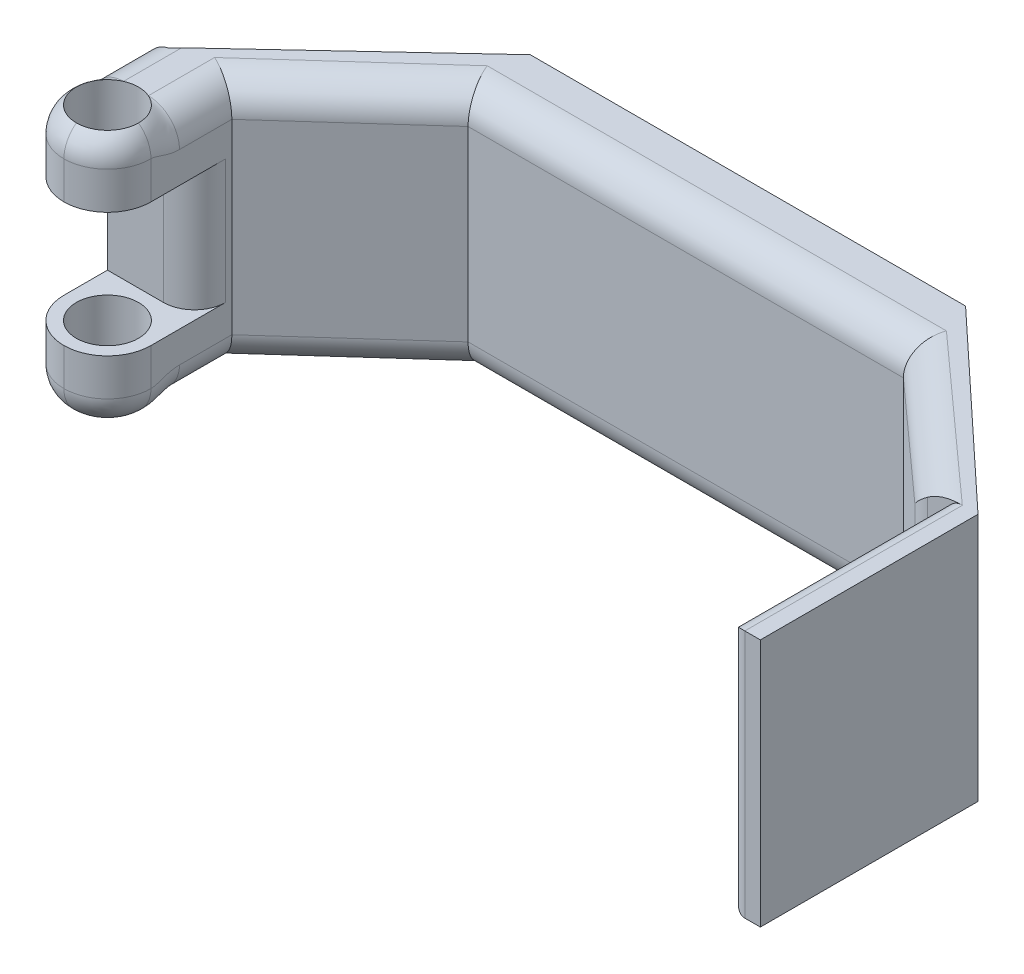
SolidWorks part; units mm, degrees
ref_plane "Front Plane" through (0, 0, 0) normal (0, 0, 1) x (1, 0, 0)
ref_plane "Top Plane" through (0, 0, 0) normal (0, 1, 0) x (1, 0, 0)
ref_plane "Right Plane" through (0, 0, 0) normal (1, 0, 0) x (0, 0, -1)
sketch "Sketch1" plane through (0, 0, 0) normal (0, 1, 0) x (1, 0, 0)
  line L0 (0, 0) -> (20, 18)
  line L1 (20, 18) -> (90, 18)
  line L2 (90, 18) -> (110, 0)
  line L3 (0, 0) -> (-10, 0)
  line L4 (-10, 0) -> (20, 28)
  line L5 (20, 28) -> (90, 28)
  line L6 (110, 0) -> (120, 0)
  line L7 (120, 0) -> (90, 28)
  dimension "D1" = 20
  dimension "D2" = 18
  dimension "D3" = 70
  dimension "D4" = 20
  dimension "D5" = 18
  dimension "D6" = 10
  dimension "D7" = 10
  dimension "D8" = 10
extrude "Boss-Extrude1" add sketch "Sketch1" along normal blind 40
sketch "Sketch2" plane through (0, 0, 0) normal (0, 0, 1) x (1, 0, 0)
  line L1 (0, 40) -> (-14, 40)
  line L2 (0, 40) -> (0, 0)
  line L3 (0, 0) -> (-14, 0)
  line L4 (-14, 40) -> (-14, 0)
  dimension "D1" = 14
extrude "Boss-Extrude2" add sketch "Sketch2" along normal blind 20
sketch "Sketch3" plane through (0, 0, 0) normal (1, 0, 0) x (0, 0, -1)
  line L0 (-20, 0) -> (-20, 40) construction
  line L1 (-20, 30) -> (-6, 30)
  line L2 (-20, 30) -> (-20, 10)
  line L3 (-20, 10) -> (-6, 10)
  line L4 (-6, 30) -> (-6, 10)
  line L5 (-20, 0) -> (0, 0) construction
  dimension "D1" = 14
  dimension "D2" = 20
  dimension "D3" = 10
extrude "Cut-Extrude2" cut sketch "Sketch3" against normal up to next
sketch "Sketch5" plane through (0, 10, 0) normal (0, 1, 0) x (1, 0, 0)
  circle A0 centre (-7, -13) radius 5
  dimension "D1" = 10
extrude "Cut-Extrude3" cut sketch "Sketch5" against normal through all and the other way through all
fillet "Fillet1" radius 7 4 edges at (-14, 5, 20) (0, 5, 20) (0, 35, 20) (-14, 35, 20)
sketch "Sketch7" plane through (0, 0, 0) normal (0, 0, 1) x (1, 0, 0)
  line L0 (110, 0) -> (120, 0) construction
  line L1 (120, 40) -> (115, 40)
  line L2 (120, 40) -> (120, 0)
  line L3 (120, 0) -> (115, 0)
  line L4 (115, 40) -> (115, 0)
extrude "Boss-Extrude3" add sketch "Sketch7" along normal blind 35
fillet "Fillet2" radius 5 12 edges at (0, 0, 6.5) (-14, 0, 6.5) (-14, 40, 6.5) (0, 40, 6.5) (0, 20, 6) (110, 20, 0) (100, 40, -9) (100, 0, -9) (55, 0, -18) (10, 0, -9) (55, 40, -18) (10, 40, -9)
fillet "Fillet3" radius 2.5 3 edges at (115, 20, 35) (115, 0, 16.3866) (115, 40, 16.3866)
